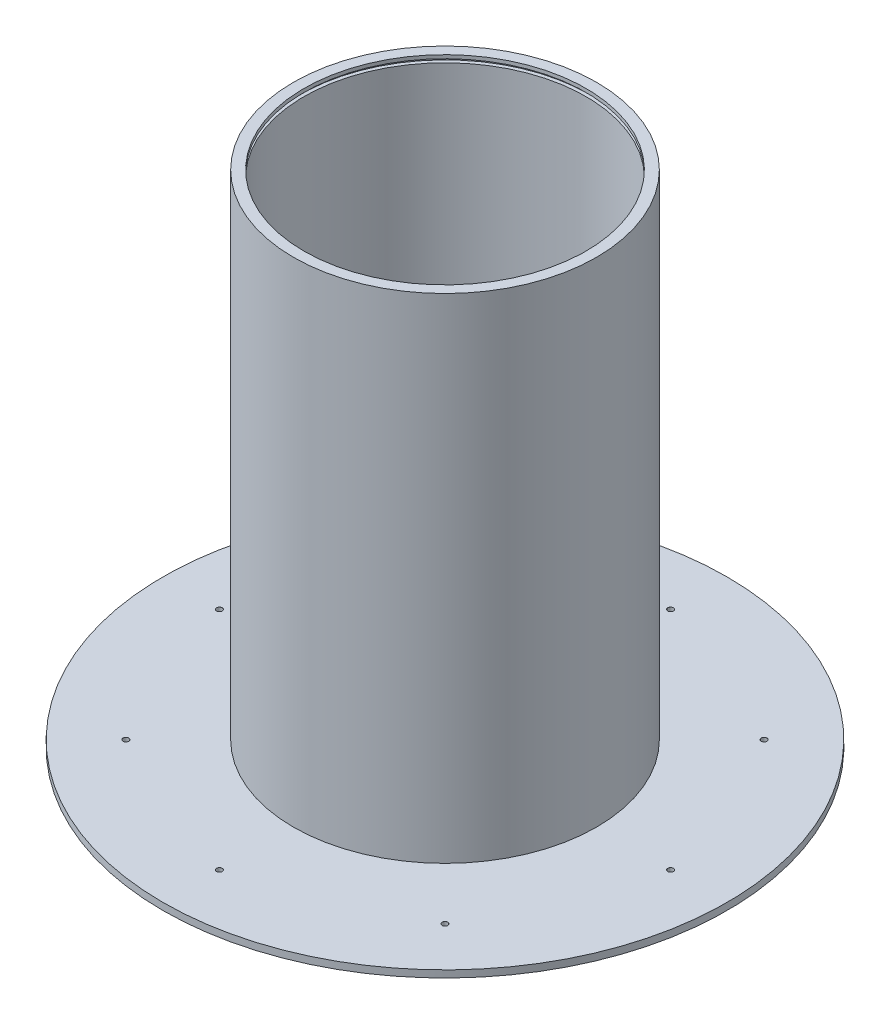
SolidWorks part; units mm, degrees
note: The reader was unsure of these and kept them because the rebuilt part matched: shared geometry of "Sketch1<3>", "Sketch1<5>".
ref_plane "Front Plane" through (0, 0, 0) normal (0, 0, 1) x (1, 0, 0)
ref_plane "Top Plane" through (0, 0, 0) normal (0, 1, 0) x (1, 0, 0)
ref_plane "Right Plane" through (0, 0, 0) normal (1, 0, 0) x (0, 0, -1)
sketch "Sketch1" plane through (0, 0, 0) normal (0, 1, 0) x (1, 0, 0)
  circle A0 centre (0, 0) radius 100
  circle A1 centre (0, 0) radius 107.5
  circle A2 centre (0, 0) radius 95
  circle A3 centre (0, 0) radius 31
  point P0 (0, 0)
  dimension "D1" = 200
  dimension "D2" = 215
  dimension "D3" = 190
  dimension "D4" = 62
extrude "Boss-Extrude1" add sketch "Sketch1" along normal blind 155 and the other way blind 200 contours A1 A0
extrude "Boss-Extrude2" add sketch "Sketch1<3>" against normal blind 17 contours A0 A2 | A2 A3
sketch "Sketch1<3>" plane through (0, 0, 0) normal (0, 1, 0) x (1, 0, 0) same geometry as "Sketch1"
extrude "Cut-Extrude1" cut sketch "Sketch1<5>" against normal blind 4 contours A2 A3
sketch "Sketch1<5>" plane through (0, 0, 0) normal (0, 1, 0) x (1, 0, 0) same geometry as "Sketch1"
ref_plane "Plane1" through (0, -17, 0) normal (0, -1, 0) x (-1, 0, 0)
sketch "Sketch2" plane through (0, -17, 0) normal (0, -1, 0) x (-1, 0, 0)
  line L0 (0, 0) -> (0, 90.7247) construction
  point P0 (0, 0)
  point P4 (0, 70)
  point P5 (49.4975, 49.4975)
  point P8 (70, 0)
  point P9 (49.4975, -49.4975)
  point P10 (0, -70)
  point P11 (-49.4975, -49.4975)
  point P12 (-70, 0)
  point P13 (-49.4975, 49.4975)
  point P14 (0, 0)
  dimension "D1" = 70
  dimension "D2" = 8
hole_wizard "Ø4.0mm Dowel Hole1" positions "Sketch3" profile "Sketch4" hole size "Ø4.0" standard "ISO"
sketch "Sketch3" plane through (0, -17, 0) normal (0, -1, 0) x (-1, 0, 0)
  point P0 (0, 70)
  point P3 (49.4975, 49.4975)
  point P6 (-49.4975, 49.4975)
  point P9 (-70, 0)
  point P12 (-49.4975, -49.4975)
  point P15 (0, -70)
  point P18 (49.4975, -49.4975)
  point P21 (70, 0)
sketch "Sketch4" plane through (0, -17, -70) normal (1, 0, 0) x (0, 0, -1)
  line L0 (0, 0) -> (0, 14.2007)
  line L1 (0, 14.2007) -> (2, 12.999)
  line L2 (2, 12.999) -> (2, 0.025)
  line L3 (2, 0.025) -> (2.025, 0)
  line L5 (2.025, 0) -> (0, 0)
  line L6 (-2, 0.025) -> (-2.025, 0) construction
  line L10 (0, 14.2007) -> (-2, 12.999) construction
  line L11 (0, -6.35) -> (0, 107.95) construction
  dimension "Hole Dia." = 4
  dimension "Hole Depth" = 12.999
  dimension "Near C'Sink Dia." = 4.05
  dimension "Near C'Sink Angle" = 90
  dimension "Drill Angle" = 118
ref_plane "Plane2" through (0, -4, 0) normal (0, 1, 0) x (1, 0, 0)
sketch "Sketch5" plane through (0, -4, 0) normal (0, 1, 0) x (1, 0, 0)
  line L0 (0, 0) -> (0, 90.7247) construction
  line L1 (46.2315, 46.2315) -> (50.6929, 45.0361)
  line L2 (0, 65.3812) -> (4, 67.6906)
  line L3 (4, 67.6906) -> (4, 72.3094)
  line L4 (4, 72.3094) -> (0, 74.6188)
  line L5 (0, 74.6188) -> (-4, 72.3094)
  line L6 (-4, 72.3094) -> (-4, 67.6906)
  line L7 (-4, 67.6906) -> (0, 65.3812)
  line L8 (50.6929, 45.0361) -> (53.9589, 48.302)
  line L9 (53.9589, 48.302) -> (52.7635, 52.7635)
  line L10 (52.7635, 52.7635) -> (48.302, 53.9589)
  line L11 (48.302, 53.9589) -> (45.0361, 50.6929)
  line L12 (45.0361, 50.6929) -> (46.2315, 46.2315)
  line L13 (65.3812, 0) -> (67.6906, -4)
  line L14 (67.6906, -4) -> (72.3094, -4)
  line L15 (72.3094, -4) -> (74.6188, 0)
  line L16 (74.6188, 0) -> (72.3094, 4)
  line L17 (72.3094, 4) -> (67.6906, 4)
  line L18 (67.6906, 4) -> (65.3812, 0)
  line L19 (46.2315, -46.2315) -> (45.0361, -50.6929)
  line L20 (45.0361, -50.6929) -> (48.302, -53.9589)
  line L21 (48.302, -53.9589) -> (52.7635, -52.7635)
  line L22 (52.7635, -52.7635) -> (53.9589, -48.302)
  line L23 (53.9589, -48.302) -> (50.6929, -45.0361)
  line L24 (50.6929, -45.0361) -> (46.2315, -46.2315)
  line L25 (0, -65.3812) -> (-4, -67.6906)
  line L26 (-4, -67.6906) -> (-4, -72.3094)
  line L27 (-4, -72.3094) -> (0, -74.6188)
  line L28 (0, -74.6188) -> (4, -72.3094)
  line L29 (4, -72.3094) -> (4, -67.6906)
  line L30 (4, -67.6906) -> (0, -65.3812)
  line L31 (-46.2315, -46.2315) -> (-50.6929, -45.0361)
  line L32 (-50.6929, -45.0361) -> (-53.9589, -48.302)
  line L33 (-53.9589, -48.302) -> (-52.7635, -52.7635)
  line L34 (-52.7635, -52.7635) -> (-48.302, -53.9589)
  line L35 (-48.302, -53.9589) -> (-45.0361, -50.6929)
  line L36 (-45.0361, -50.6929) -> (-46.2315, -46.2315)
  line L37 (-65.3812, 0) -> (-67.6906, 4)
  line L38 (-67.6906, 4) -> (-72.3094, 4)
  line L39 (-72.3094, 4) -> (-74.6188, 0)
  line L40 (-74.6188, 0) -> (-72.3094, -4)
  line L41 (-72.3094, -4) -> (-67.6906, -4)
  line L42 (-67.6906, -4) -> (-65.3812, 0)
  line L43 (-46.2315, 46.2315) -> (-45.0361, 50.6929)
  line L44 (-45.0361, 50.6929) -> (-48.302, 53.9589)
  line L45 (-48.302, 53.9589) -> (-52.7635, 52.7635)
  line L46 (-52.7635, 52.7635) -> (-53.9589, 48.302)
  line L47 (-53.9589, 48.302) -> (-50.6929, 45.0361)
  line L48 (-50.6929, 45.0361) -> (-46.2315, 46.2315)
  circle A0 centre (0, 70) radius 4 construction
  point P0 (0, 0)
  point P4 (0, 70)
  point P5 (49.4975, 49.4975)
  point P8 (70, 0)
  point P9 (49.4975, -49.4975)
  point P10 (0, -70)
  point P11 (-49.4975, -49.4975)
  point P12 (-70, 0)
  point P13 (-49.4975, 49.4975)
  point P14 (0, 0)
  point P67 (0, 0)
  dimension "D1" = 70
  dimension "D2" = 8
  dimension "D3" = 8
extrude "Cut-Extrude2" cut sketch "Sketch5" against normal blind 5
ref_plane "Plane3" through (0, -200, 0) normal (0, -1, 0) x (-1, 0, 0)
sketch "Sketch8" plane through (0, -200, 0) normal (0, -1, 0) x (-1, 0, 0)
  line L0 (0, 0) -> (0, 81.9785) construction
  circle A0 centre (0, 0) radius 200
  circle A1 centre (0, 0) radius 100
  point P3 (0, 160)
  point P4 (113.1371, 113.1371)
  point P7 (160, 0)
  point P8 (113.1371, -113.1371)
  point P9 (0, -160)
  point P10 (-113.1371, -113.1371)
  point P11 (-160, 0)
  point P12 (-113.1371, 113.1371)
  point P13 (0, 0)
  dimension "D3" = 200
  dimension "D4" = 400
  dimension "D1" = 160
  dimension "D2" = 8
extrude "Boss-Extrude3" add sketch "Sketch8" against normal blind 5
sketch "Sketch9" plane through (0, -200, 0) normal (0, -1, 0) x (-1, 0, 0)
  line L0 (0, 0) -> (0, 81.9785) construction
  circle A0 centre (0, 0) radius 200
  circle A1 centre (0, 0) radius 100
  point P3 (0, 160)
  point P4 (113.1371, 113.1371)
  point P7 (160, 0)
  point P8 (113.1371, -113.1371)
  point P9 (0, -160)
  point P10 (-113.1371, -113.1371)
  point P11 (-160, 0)
  point P12 (-113.1371, 113.1371)
  point P13 (0, 0)
  dimension "D3" = 200
  dimension "D4" = 400
  dimension "D1" = 160
  dimension "D2" = 8
hole_wizard "Ø4.0mm Dowel Hole2" positions "Sketch10" profile "Sketch11" hole size "Ø4.0" standard "ISO"
sketch "Sketch10" plane through (0, -195, 0) normal (0, 1, 0) x (1, 0, 0)
  point P0 (160, 0)
  point P3 (113.1371, 113.1371)
  point P6 (0, 160)
  point P9 (-113.1371, 113.1371)
  point P12 (-160, 0)
  point P15 (-113.1371, -113.1371)
  point P18 (113.1371, -113.1371)
  point P21 (0, -160)
sketch "Sketch11" plane through (160, -195, 0) normal (1, 0, 0) x (0, 0, 1)
  line L0 (0, 0) -> (0, 6.2007)
  line L1 (0, 6.2007) -> (2, 4.999)
  line L2 (2, 4.999) -> (2, 0.025)
  line L3 (2, 0.025) -> (2.025, 0)
  line L5 (2.025, 0) -> (0, 0)
  line L6 (-2, 0.025) -> (-2.025, 0) construction
  line L10 (0, 6.2007) -> (-2, 4.999) construction
  line L11 (0, -6.35) -> (0, 107.95) construction
  dimension "Hole Dia." = 4
  dimension "Hole Depth" = 4.999
  dimension "Near C'Sink Dia." = 4.05
  dimension "Near C'Sink Angle" = 90
  dimension "Drill Angle" = 118
ref_plane "Plane4" through (0, 150, 0) normal (0, 1, 0) x (1, 0, 0)
sketch "Sketch12" plane through (0, 150, 0) normal (0, 1, 0) x (1, 0, 0)
  circle A0 centre (0, 0) radius 102.5
  dimension "D1" = 205
extrude "Cut-Extrude3" cut sketch "Sketch12" along normal blind 2.5
